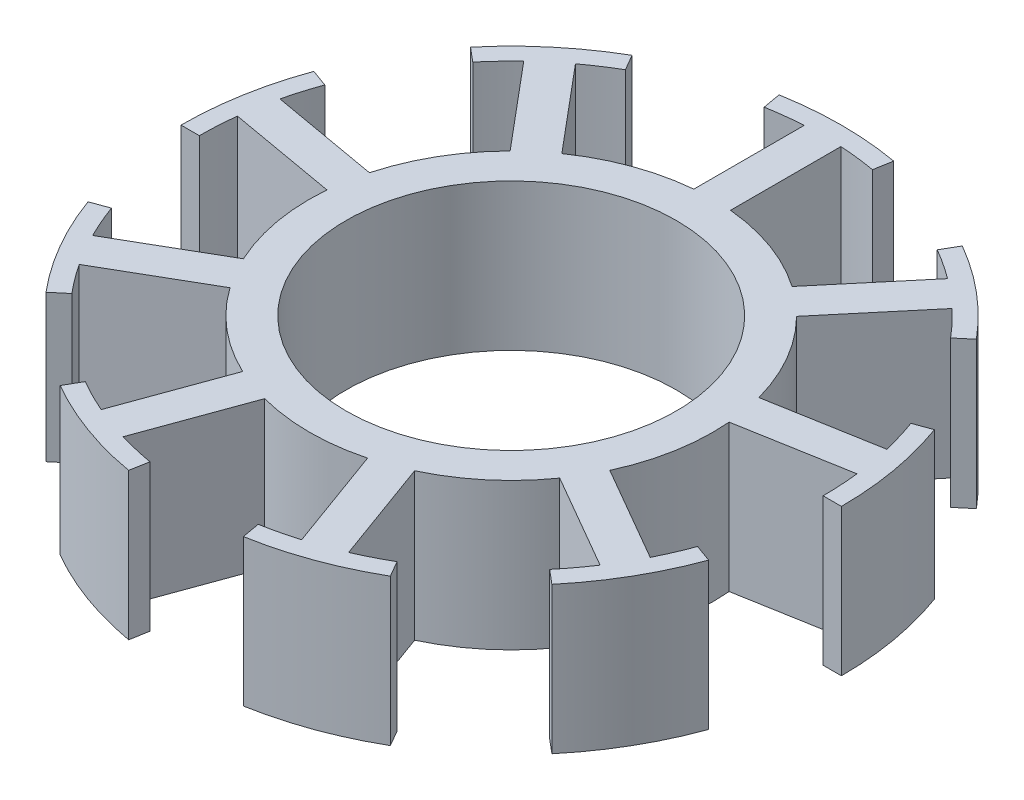
SolidWorks part; units mm, degrees
ref_plane "Front Plane" through (0, 0, 0) normal (0, 0, 1) x (1, 0, 0)
ref_plane "Top Plane" through (0, 0, 0) normal (0, 1, 0) x (1, 0, 0)
ref_plane "Right Plane" through (0, 0, 0) normal (1, 0, 0) x (0, 0, -1)
sketch "Sketch1" plane through (0, 0, 0) normal (0, 1, 0) x (1, 0, 0)
  line L0 (-1, 10.9545) -> (-1, 16.9706)
  line L1 (0, 0) -> (0, 13.6776) construction
  line L2 (1, 10.9545) -> (1, 16.9706)
  line L3 (-3.1257, 17.7265) -> (-2.952, 16.7417)
  line L4 (3.1257, 17.7265) -> (2.952, 16.7417)
  circle A0 centre (0, 0) radius 9
  circle A1 centre (0, 0) radius 11
  arc A2 (2.952, 16.7417) -> (1, 16.9706) centre (0, 0) ccw
  arc A3 (3.1257, 17.7265) -> (-3.1257, 17.7265) centre (0, 0) ccw
  arc A4 (-1, 16.9706) -> (-2.952, 16.7417) centre (0, 0) ccw
  dimension "D1" = 18
  dimension "D2" = 2
  dimension "D3" = 36
  dimension "D4" = 1
  dimension "D5" = 20
  dimension "D6" = 2
extrude "Boss-Extrude1" add sketch "Sketch1" along normal blind 8 contours A0 A1 region at (0, 0, -10.6889)
extrude "Boss-Extrude4" add sketch "Sketch1<3>" along normal blind 8 contours A4 L0 A1 L2 A2 L4 A3 L3 region at (0, 0, -15.1434)
sketch "Sketch1<3>" plane through (0, 0, 0) normal (0, 1, 0) x (1, 0, 0) same geometry as "Sketch1"
pattern_circular "CirPattern2" count 9 over 360 about axis through (0, 8, 0) along (0, -1, 0) of "Boss-Extrude4"
